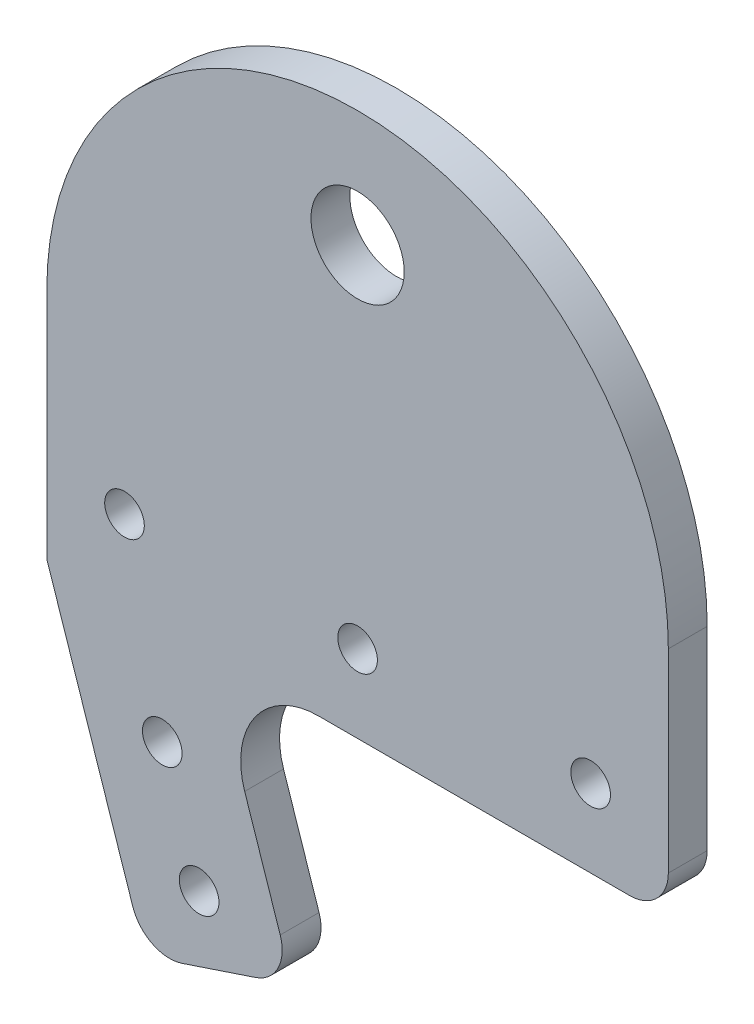
SolidWorks part; units mm, degrees
ref_plane "正面" through (0, 0, 0) normal (0, 0, 1) x (1, 0, 0)
ref_plane "平面" through (0, 0, 0) normal (0, 1, 0) x (1, 0, 0)
ref_plane "右側面" through (0, 0, 0) normal (1, 0, 0) x (0, 0, -1)
sketch "ｽｹｯﾁ1" plane through (0, 0, 0) normal (0, 0, 1) x (1, 0, 0)
  line L0 (-40, -55) -> (40, -55)
  line L1 (-40, -25) -> (-40, -55)
  line L2 (40, -25) -> (40, -55)
  line L3 (0, 0) -> (0, -25) construction
  line L4 (-30, -25) -> (-30, -45) construction
  line L5 (-30, -45) -> (30, -45) construction
  line L6 (30, -45) -> (30, -25) construction
  line L7 (-40, -25) -> (40, -25) construction
  circle A0 centre (0, 0) radius 6
  arc A2 (-40, -25) -> (40, -25) centre (0, -25) cw
  circle A3 centre (-30, -45) radius 2.55
  circle A4 centre (0, -45) radius 2.55
  circle A5 centre (30, -45) radius 2.55
  dimension "D1" = 80
  dimension "D2" = 12
  dimension "D3" = 30
  dimension "D4" = 25
  dimension "D8" = 5.1
  dimension "D5" = 10
  dimension "D6" = 10
  dimension "D7" = 10
extrude "ﾎﾞｽ - 押し出し1" add sketch "ｽｹｯﾁ1" along normal blind 5
sketch "ｽｹｯﾁ2" plane through (0, 0, 5) normal (0, 0, 1) x (1, 0, 0)
  line L0 (-27.3509, -92.9473) -> (-40, -55)
  line L1 (-37.8918, -61.3246) -> (0.0555, -175.1666) construction
  line L2 (-27.3509, -92.9473) -> (-8.3772, -86.6228)
  line L3 (-18.9181, -55) -> (19.0292, -168.842) construction
  line L4 (-8.3772, -86.6228) -> (-18.9181, -55)
  line L5 (-40, -55) -> (40, -55) construction
  line L6 (-18.9181, -55) -> (-20.3412, -55.4743) construction
  line L7 (-18.9181, -55) -> (-40, -55)
  line L8 (-17.8641, -89.7851) -> (-29.4591, -55) construction
  circle A0 centre (-20.3939, -82.1956) radius 2.55
  circle A1 centre (-25.1373, -67.9653) radius 2.55
  dimension "D1" = 8
  dimension "D2" = 5.1
  dimension "D4" = 15
  dimension "D3" = 40
extrude "ﾎﾞｽ - 押し出し2" add sketch "ｽｹｯﾁ2" against normal up to surface (5 mm away) up to face at (-27.45, -45, 0)
fillet "ﾌｨﾚｯﾄ1" radius 10 1 edges at (-18.9181, -55, 2.5)
fillet "ﾌｨﾚｯﾄ2" radius 5 3 edges at (40, -55, 2.5) (-8.3772, -86.6228, 2.5) (-27.3509, -92.9473, 2.5)
